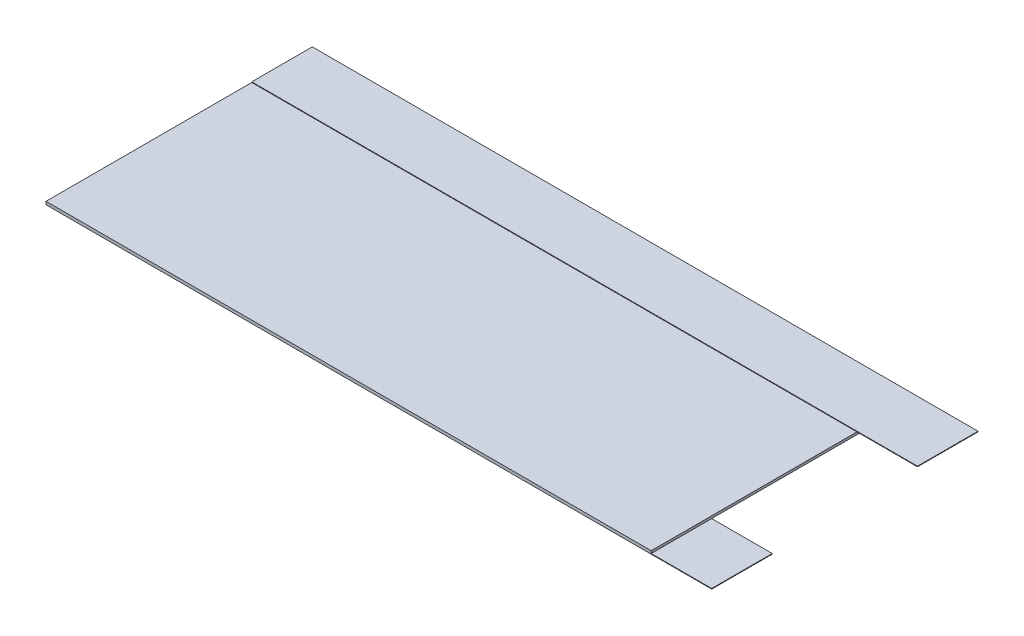
SolidWorks part; units mm, degrees
ref_plane "Front Plane" through (0, 0, 0) normal (0, 0, 1) x (1, 0, 0)
ref_plane "Top Plane" through (0, 0, 0) normal (0, 1, 0) x (1, 0, 0)
ref_plane "Right Plane" through (0, 0, 0) normal (1, 0, 0) x (0, 0, -1)
sketch "Sketch1" plane through (0, 0, 0) normal (0, 1, 0) x (1, 0, 0)
  line L1 (-25, -11) -> (25, -11)
  line L2 (-25, -11) -> (-25, 11)
  line L3 (-25, 11) -> (25, 11)
  line L4 (25, -11) -> (25, 11)
  line L5 (-25, -11) -> (25, 11) construction
  line L6 (-25, 11) -> (25, -11) construction
  point P0 (0, 0)
  dimension "D1" = 22
  dimension "D2" = 50
extrude "Boss-Extrude1" add sketch "Sketch1" along normal blind 0.1
sketch "Sketch2" plane through (0, 0.1, 0) normal (0, 1, 0) x (1, 0, 0)
  line L1 (-25, 11) -> (30, 11)
  line L2 (-25, 11) -> (-25, 6)
  line L3 (-25, 6) -> (30, 6)
  line L4 (30, 11) -> (30, 6)
  dimension "D1" = 5
  dimension "D2" = 55
extrude "Boss-Extrude2" add sketch "Sketch2" along normal blind 0.05
ref_axis "Axis1" through (-27.7501, 0, 0) along (1, 0, 0)
pattern_circular "CirPattern1" count 2 over 360 about axis through (-27.7501, 0, 0) along (1, 0, 0) of "Boss-Extrude2"
combine bodies "Combine2" operation type add bodies to combine 103 102
